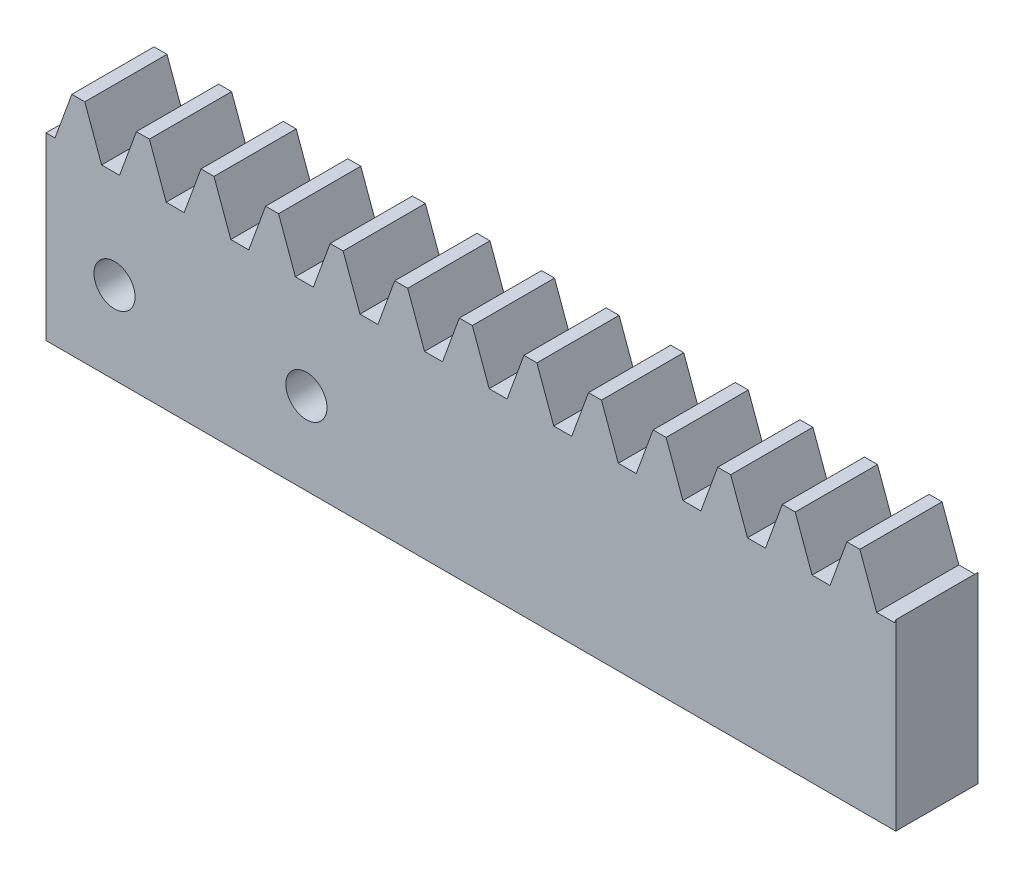
SolidWorks part; units mm, degrees
extrude "Blank" add sketch "BlankSke" against normal blind 6
sketch "BlankSke" plane through (0, 0, 0) normal (0, 0, 1) x (1, 0, 0)
  line L1 (0, 0) -> (62, 0)
  line L2 (0, 0) -> (0, 16.5)
  line L3 (0, 16.5) -> (62, 16.5)
  line L4 (62, 0) -> (62, 16.5)
  dimension "Length" = 62
ref_plane "Plane1" through (0, 0, 0) normal (0, 0, 1) x (1, 0, 0)
ref_plane "Plane2" through (0, 0, 0) normal (0, 1, 0) x (1, 0, 0)
ref_plane "Plane3" through (0, 0, 0) normal (1, 0, 0) x (0, 0, -1)
sketch "HoldingSke" plane through (0, 0, 0) normal (0, 1, 0) x (1, 0, 0)
  line L0 (0, 0) -> (0.0928, 0.6602)
  line L1 (-15, 0) -> (100, 0) construction
  line L2 (0, 0) -> (-2.1039, 2.3779)
  line L3 (0, 0) -> (-11.863, 4.5341)
  line L4 (0, 0) -> (8.3417, 2.2351)
  line L5 (0, 0) -> (-23.7986, -8.8762)
  line L6 (0, 0) -> (-10.5278, -7.1032)
  line L9 (-71.009, 38.7566) -> (-12.748, 59.9619)
  line L10 (-76.2, 3.8779) -> (-61.2, 3.8779)
  line L11 (0, 0) -> (-6, 0)
  line L12 (-76.2, 101.6) -> (-76.147, 101.6)
  line L13 (24.9733, 27.94) -> (52.9518, 28.4284)
  line L14 (24.9733, 27.94) -> (24.9743, 27.94)
  line L15 (24.9733, 27.94) -> (100.4006, 29.5858)
  circle A0 centre (0, 0) radius 19.05
  circle A1 centre (0, 0) radius 7.5
  circle A2 centre (0, 0) radius 12.7
  dimension "Num_teeth" = 15
  dimension "Width" = 6
  dimension "Length" = 62
  dimension "Pitch_height" = 15
sketch "TooCutSkeIll" plane through (0, 0, 0) normal (0, 0, 1) x (1, 0, 0)
  line L0 (-1.8687, 16.4605) -> (-0.7447, 13.3724)
  line L1 (-0.3914, 13.125) -> (0.3914, 13.125)
  line L2 (0.7447, 13.3724) -> (1.8687, 16.4605)
  line L3 (62, 16.5) -> (0, 16.5) construction
  line L4 (0, 0) -> (0, 64.897) construction
  line L5 (-13.208, 15) -> (12.954, 15) construction
  line L6 (0, 0) -> (62, 0) construction
  line L7 (1.3371, 15) -> (1.3371, 48.7463) construction
  line L8 (-1.3371, 15) -> (-1.3371, 48.7463) construction
  line L9 (1.9251, 16.5) -> (1.9251, 16.5254)
  line L10 (-1.9251, 16.5) -> (-1.9251, 16.5254)
  line L11 (-1.9251, 16.5254) -> (1.9251, 16.5254)
  arc A0 (0.3914, 13.125) -> (0.7447, 13.3724) centre (0.3914, 13.501) ccw
  arc A1 (-0.7447, 13.3724) -> (-0.3914, 13.125) centre (-0.3914, 13.501) ccw
  arc A2 (1.9251, 16.5) -> (1.8687, 16.4605) centre (1.9251, 16.44) ccw
  arc A3 (-1.8687, 16.4605) -> (-1.9251, 16.5) centre (-1.9251, 16.44) ccw
  dimension "Addendum_plus" = 1.5254
  dimension "Pitch_height" = 15
  dimension "Pressure_angle" = 20
  dimension "Gap_width" = 2.6742
  dimension "Dedendum" = 1.875
extrude "ToothCutIll" [suppressed] cut sketch "TooCutSkeIll" against normal through all
sketch "TooCutSkeSim" plane through (0, 0, 0) normal (0, 0, 1) x (1, 0, 0)
  line L0 (0.6547, 13.125) -> (-0.6547, 13.125)
  line L1 (1.8923, 16.5254) -> (0.6547, 13.125)
  line L2 (0, 17.4625) -> (0, 53.467) construction
  line L3 (1.8923, 16.5254) -> (-1.8923, 16.5254)
  line L6 (-1.8923, 16.5254) -> (-0.6547, 13.125)
  line L9 (-1.3371, 15) -> (1.3371, 15) construction
  line L10 (0, 0) -> (62, 0) construction
  line L11 (1.3371, 15) -> (1.3371, 53.467) construction
  line L12 (-1.3371, 15) -> (-1.3371, 53.467) construction
  dimension "Addendum_plus" = 1.5254
  dimension "Pitch_height" = 15
  dimension "Pressure_angle" = 20
  dimension "Gap_width" = 2.6742
  dimension "Dedendum" = 1.875
extrude "ToothCutSim" cut sketch "TooCutSkeSim" against normal through all
pattern_linear "TeethCuts" count 15 spacing 4.7124 along (1, 0, 0) of "ToothCutIll", "ToothCutSim"
sketch "Esquisse2" plane through (0, 0, 0) normal (0, 0, 1) x (1, 0, 0)
  line L0 (-9.3907, 6) -> (34.1411, 6) construction
  line L1 (0, 13.125) -> (0, 0) construction
  line L2 (0, 0) -> (62, 0) construction
  circle A0 centre (5, 6) radius 1.5
  circle A1 centre (19, 6) radius 1.5
  dimension "D1" = 3
  dimension "D2" = 3
  dimension "D3" = 14
  dimension "D4" = 5
  dimension "D5" = 6
extrude "Enlèv. mat.-Extru.1" cut sketch "Esquisse2" against normal blind 6
equation "' \"Module@HoldingSke\" = 6.35"
equation "' \"Num_teeth@HoldingSke\" = 12"
equation "' \"Ap@HoldingSke\" =  20"
equation "' \"Ap@HoldingSke\" = 20"
equation "' \"Width@HoldingSke\" = 0.25 * 25.4"
equation "' \"Show_teeth@HoldingSke\" = 500"
equation "' \"Backlash@HoldingSke\" = 0.009 * 25.4"
equation "' \"Addendum_fac@HoldingSke\" = 1.0"
equation "' \"Dedendum_fac@HoldingSke\" = 1.25"
equation "' \"Dedendum_add@HoldingSke\" = 0.00005 * 25.4"
equation "' \"Clearance_fac@HoldingSke\" = 0.25"
equation "' \"Pitch_height@HoldingSke\" = 1 * 25.4"
equation "' \"Length@HoldingSke\" = 4.71 * 25.4"
equation "\"Pitch@HoldingSke\" = 1 / \"Module@HoldingSke\""
equation "\"MPH@HoldingSke\" = \"Dedendum_fac@HoldingSke\" / \"Pitch@HoldingSke\" + 2 * \"Dedendum_add@HoldingSke\" + 0.002 * 25.4"
equation "\"MPH@HoldingSke\" = ((sgn( \"MPH@HoldingSke\" - \"Pitch_height@HoldingSke\")+1)*( \"MPH@HoldingSke\" - \"Pitch_height@HoldingSke\"))/2 + \"Pitch_height@HoldingSke\""
equation "\"Blank_height@BlankSke\" = \"Pitch_height@HoldingSke\" + \"Addendum_fac@HoldingSke\"  / \"Pitch@HoldingSke\" "
equation "\"Length@BlankSke\" =  \"Length@HoldingSke\""
equation "\"Face_width@Blank\" = \"Width@HoldingSke\""
equation "\"Pressure_angle@TooCutSkeIll\" = \"Ap@HoldingSke\""
equation "\"Addendum_plus@TooCutSkeIll\" =  \"Addendum_fac@HoldingSke\"  / \"Pitch@HoldingSke\" + 0.001 *25.4"
equation "\"Dedendum@TooCutSkeIll\" = \"Dedendum_fac@HoldingSke\"  / \"Pitch@HoldingSke\""
equation "\"Pitch_height@TooCutSkeIll\" =  \"MPH@HoldingSke\""
equation "\"Gap_width@TooCutSkeIll\" = 3.14159265 / 2 / \"Pitch@HoldingSke\" + 6 * \"Backlash@HoldingSke\""
equation "\"Pressure_angle@TooCutSkeSim\" = \"Ap@HoldingSke\""
equation "\"Addendum_plus@TooCutSkeSim\" =  \"Addendum_fac@HoldingSke\"  / \"Pitch@HoldingSke\" + 0.001 * 25.4"
equation "\"Dedendum@TooCutSkeSim\" = \"Dedendum_fac@HoldingSke\"  / \"Pitch@HoldingSke\""
equation "\"Pitch_height@TooCutSkeSim\" =  \"MPH@HoldingSke\""
equation "\"Gap_width@TooCutSkeSim\" = 3.14159265 / 2 / \"Pitch@HoldingSke\" + 6 * \"Backlash@HoldingSke\""
equation "\"Root_fillet@TooCutSkeIll\" = \"Clearance_fac@HoldingSke\" / \"Pitch@HoldingSke\" + \"Dedendum_add@HoldingSke\""
equation "\"Break_rad@TooCutSkeIll\" = 0.02 / \"Pitch@HoldingSke\" * 2"
equation "\"Linear_pitch@TeethCuts\" = 3.14159265 / \"Pitch@HoldingSke\""
equation "\"Num_teeth@HoldingSke\" = int( ( \"Length@HoldingSke\" + 0 ) / (3.14159265 / \"Pitch@HoldingSke\")) + 0.9999  + 1"
equation " \"Num_teeth@TeethCuts\" = int( \"Show_teeth@HoldingSke\" ) + 1"
equation " \"Num_teeth@TeethCuts\" = ((sgn( \"Num_teeth@TeethCuts\" - \"Num_teeth@HoldingSke\" )-1)*( \"Num_teeth@TeethCuts\" - \"Num_teeth@HoldingSke\" ))/-2+ \"Num_teeth@HoldingSke\""
equation " \"Num_teeth@TeethCuts\" = ((sgn( \"Num_teeth@TeethCuts\" - 2.0)+1)*( \"Num_teeth@TeethCuts\" - 2.0))/2 +2.0"
